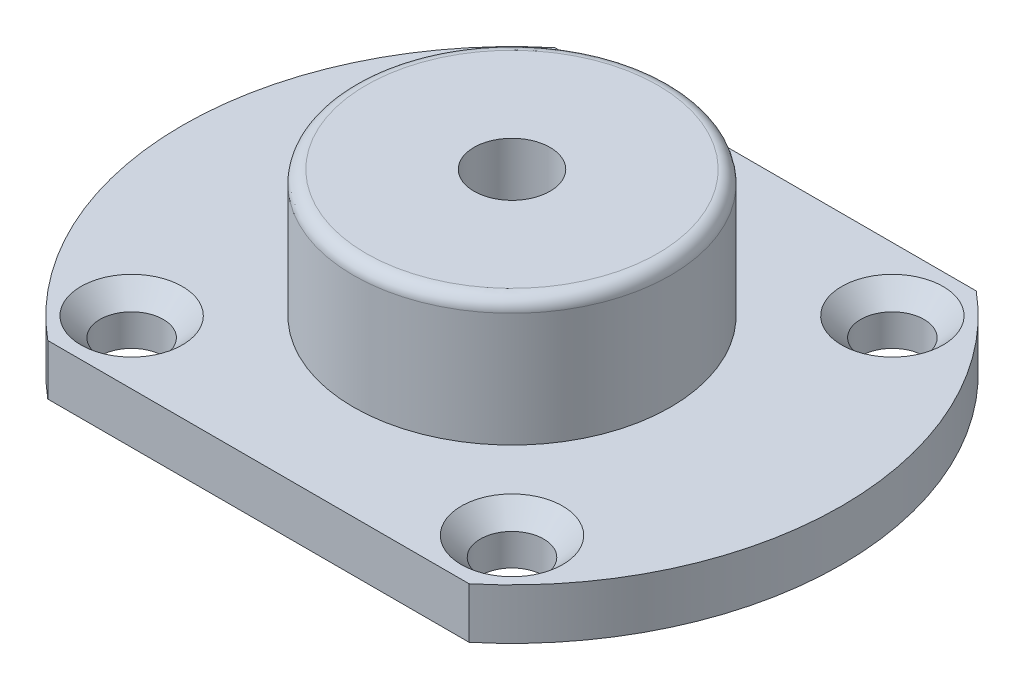
SolidWorks part; units mm, degrees
material "Легированная сталь (SS)"
ref_plane "Спереди" through (0, 0, 0) normal (0, 0, 1) x (1, 0, 0)
ref_plane "Сверху" through (0, 0, 0) normal (0, 1, 0) x (1, 0, 0)
ref_plane "Справа" through (0, 0, 0) normal (1, 0, 0) x (0, 0, -1)
sketch "Эскиз1" plane through (0, 0, 0) normal (0, 1, 0) x (1, 0, 0)
  circle A0 centre (0, 0) radius 26
  dimension "D1" = 52
extrude "Бобышка-Вытянуть1" add sketch "Эскиз1" along normal blind 4
sketch "Эскиз2" plane through (0, 4, 0) normal (0, 1, 0) x (1, 0, 0)
  line L1 (-32.8601, -20) -> (32.8601, -20)
  line L2 (-32.8601, -20) -> (-32.8601, 20)
  line L3 (-32.8601, 20) -> (32.8601, 20)
  line L4 (32.8601, -20) -> (32.8601, 20)
  line L5 (0, 20) -> (0, -20) construction
  line L6 (-32.8601, 0) -> (32.8601, 0) construction
  point P0 (0, 0)
  dimension "D1" = 40
extrude "Вырез-Вытянуть1" cut sketch "Эскиз2" against normal blind 4 flip side to cut
sketch "Эскиз3" plane through (0, 4, 0) normal (0, 1, 0) x (1, 0, 0)
  circle A0 centre (0, 0) radius 12.5
  dimension "D1" = 25
extrude "Бобышка-Вытянуть2" add sketch "Эскиз3" along normal blind 10
fillet "Скругление1" radius 1 1 edges at (0, 14, 12.5)
sketch "Эскиз4" plane through (0, 14, 0) normal (0, 1, 0) x (1, 0, 0)
  circle A0 centre (0, 0) radius 3
  dimension "D1" = 6
extrude "Вырез-Вытянуть2" cut sketch "Эскиз4" against normal up to next
sketch "Эскиз5" plane through (0, 4, 0) normal (0, 1, 0) x (1, 0, 0)
  line L0 (0, 6.8569) -> (0, 0) construction
  line L1 (0, 0) -> (5.9462, 0) construction
  circle A0 centre (-15, 15) radius 2.5
  circle A1 centre (15, 15) radius 2.5
  circle A2 centre (15, -15) radius 2.5
  circle A3 centre (-15, -15) radius 2.5
  dimension "D1" = 5
  dimension "D2" = 30
  dimension "D3" = 30
extrude "Вырез-Вытянуть3" cut sketch "Эскиз5" against normal up to next
chamfer "Фаска1" distance 1.5 angle 45 4 edges at (15, 4, -12.5) (15, 4, 17.5) (-15, 4, 17.5) (-15, 4, -12.5)
